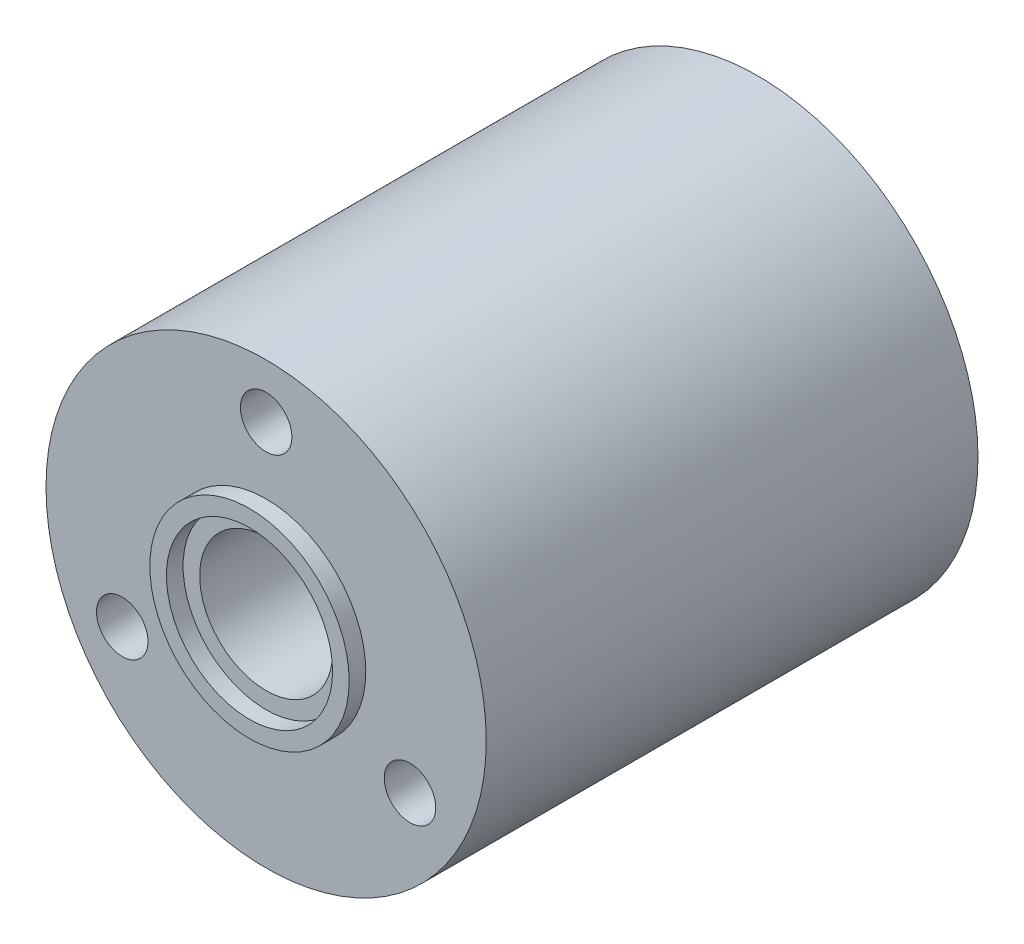
SolidWorks part; units mm, degrees
ref_plane "Front Plane" through (0, 0, 0) normal (0, 0, 1) x (1, 0, 0)
ref_plane "Top Plane" through (0, 0, 0) normal (0, 1, 0) x (1, 0, 0)
ref_plane "Right Plane" through (0, 0, 0) normal (1, 0, 0) x (0, 0, -1)
sketch "Sketch1" plane through (0, 0, 0) normal (0, 0, 1) x (1, 0, 0)
  circle A0 centre (0, 0) radius 13.25
  circle A1 centre (0, 10) radius 1.55
  circle A2 centre (8.6603, -5) radius 1.55
  circle A3 centre (-8.6603, -5) radius 1.55
  circle A4 centre (0, 0) radius 4
  circle A5 centre (0, 0) radius 5
  dimension "D1" = 26.5
  dimension "D2" = 3.1
  dimension "D5" = 8
  dimension "D3" = 10
  dimension "D6" = 1
  dimension "D4" = 3
extrude "Boss-Extrude1" add sketch "Sketch1" along normal mid plane 29.6 contours A0 A5 A3 A2 A1 | A5 A4 region at (-12.8752, 0, 0) region at (-4.8586, 0, 0)
extrude "Extrude-Thin1" add sketch "Sketch1<3>" along normal mid plane 31.6 thin contours A5 thin type one direction wall 1
sketch "Sketch1<3>" plane through (0, 0, 0) normal (0, 0, 1) x (1, 0, 0) same geometry as "Sketch1"
